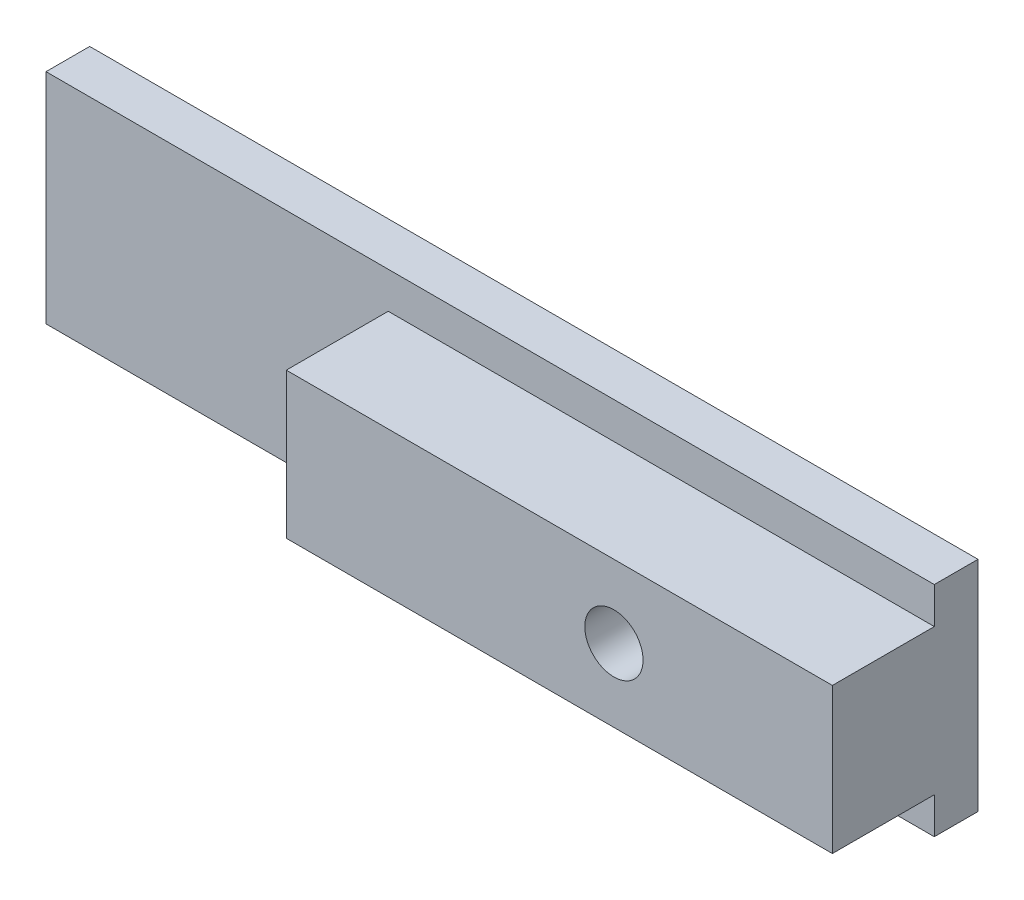
SolidWorks part; units mm, degrees
ref_plane "Piano frontale" through (0, 0, 0) normal (0, 0, 1) x (1, 0, 0)
ref_plane "Piano superiore" through (0, 0, 0) normal (0, 1, 0) x (1, 0, 0)
ref_plane "Piano destro" through (0, 0, 0) normal (1, 0, 0) x (0, 0, -1)
sketch "Schizzo1" plane through (0, 0, 0) normal (0, 0, 1) x (1, 0, 0)
  line L1 (61, -15) -> (-61, -15)
  line L2 (61, -15) -> (61, 15)
  line L3 (61, 15) -> (-61, 15)
  line L4 (-61, -15) -> (-61, 15)
  line L5 (61, -15) -> (-61, 15) construction
  line L6 (61, 15) -> (-61, -15) construction
  point P0 (0, 0)
  dimension "D1" = 122
  dimension "D2" = 30
extrude "Estrusione-Estrusione1" add sketch "Schizzo1" along normal blind 6
sketch "Schizzo2" plane through (0, 0, 6) normal (0, 0, 1) x (1, 0, 0)
  line L0 (61, -15) -> (61, 15) construction
  line L1 (-14, 10) -> (61, 10)
  line L2 (-14, 10) -> (-14, -10)
  line L3 (-14, -10) -> (61, -10)
  line L4 (61, 10) -> (61, -10)
  line L5 (-14, 10) -> (61, -10) construction
  line L6 (-14, -10) -> (61, 10) construction
  point P0 (23.5, 0)
  point P7 (61, 0)
  dimension "D1" = 75
  dimension "D2" = 20
extrude "Estrusione-Estrusione2" add sketch "Schizzo2" along normal blind 14
sketch "Schizzo3" plane through (0, 0, 20) normal (0, 0, 1) x (1, 0, 0)
  line L0 (61, 0) -> (31, 0) construction
  line L1 (61, -10) -> (61, 10) construction
  circle A0 centre (31, 0) radius 4
  dimension "D2" = 8
  dimension "D1" = 30
extrude "Taglio-Estrusione1" cut sketch "Schizzo3" against normal blind 9
hole_wizard "Foro per Vite M8-2" positions "Schizzo3D2" profile "Schizzo8" hole size "M8" standard "Ansi Metric" end condition through all
sketch3d "Schizzo3D2"
  line L0 (31, 0, 11) -> (31, 0, 20) construction
  point P0 (31, 0, 11)
sketch "Schizzo8" plane through (31, 0, 11) normal (1, 0, 0) x (0, -1, 0)
  line L0 (0, 0) -> (0, 11)
  line L1 (0, 11) -> (4.2, 11)
  line L2 (4.2, 11) -> (4.2, 0)
  line L5 (4.2, 0) -> (0, 0)
  line L11 (0, -6.35) -> (0, 107.95) construction
  dimension "Thru Hole Dia." = 8.4
  dimension "Thru Hole Depth" = 11
thread "Filettatura2" pitch 1 method cut profile "Profilo filettatura2" start angle 0, offset 0, length 11, pitch 1, diameter 8.4
ref_plane "Piano2" through (35.2, 0, 0) normal (0, -1, 0) x (1, 0, 0)
sketch "Profilo filettatura2" plane through (35.2, 0, 0) normal (0, -1, 0) x (1, 0, 0)
  line L0 (0, 0) -> (0, 1) construction
  line L1 (0, 0) -> (0.5413, 0.3125)
  line L2 (0.5413, 0.3125) -> (0.5413, 0.4375)
  line L3 (0.5413, 0.4375) -> (0, 0.75)
  line L4 (0.5413, 0.375) -> (0, 0.375) construction
  line L11 (0, 0) -> (0, 0.75)
  point P2 (0, 0)
  dimension "Pitch" = 1
  dimension "Profile_Angle" = 60
  dimension "Profile_Land" = 0.125
  dimension "Profile_Height" = 0.5413
